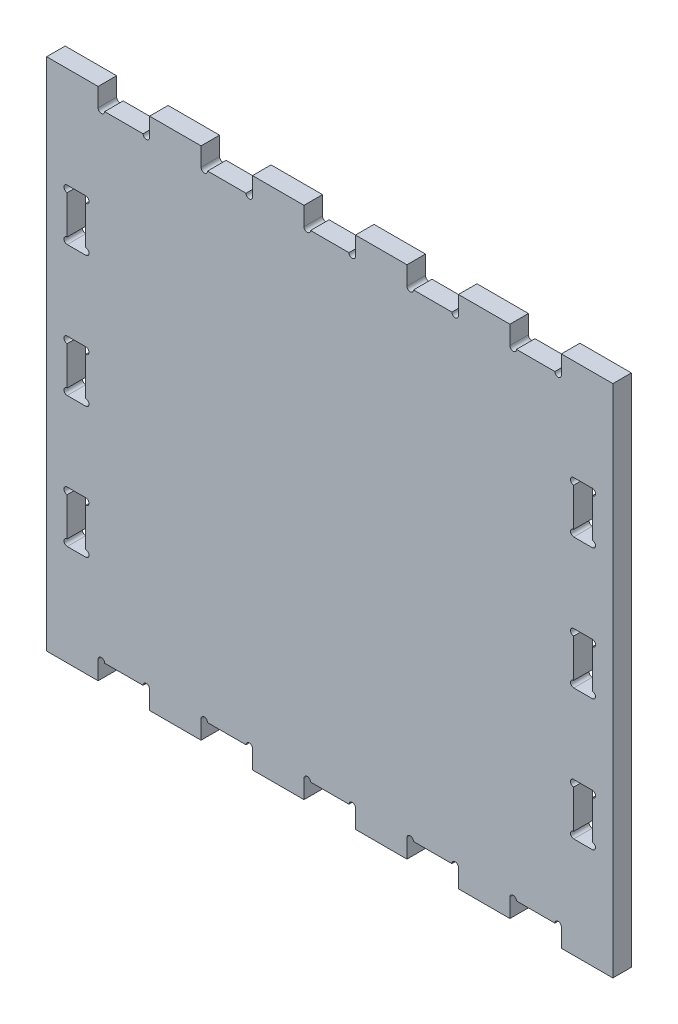
SolidWorks part; units mm, degrees
ref_plane "Piano frontale" through (0, 0, 0) normal (0, 0, 1) x (1, 0, 0)
ref_plane "Piano superiore" through (0, 0, 0) normal (0, 1, 0) x (1, 0, 0)
ref_plane "Piano destro" through (0, 0, 0) normal (1, 0, 0) x (0, 0, -1)
sketch "Schizzo2" plane through (0, 0, 0) normal (0, 0, 1) x (1, 0, 0)
  line L0 (-275, -250) -> (-275, 250)
  line L1 (-275, 250) -> (-225, 250)
  line L2 (-225, 250) -> (-225, 232)
  line L3 (-218.65, 232) -> (-181.35, 232)
  line L4 (-175, 232) -> (-175, 250)
  line L5 (-175, 250) -> (-125, 250)
  line L6 (-125, 250) -> (-125, 232)
  line L7 (-118.65, 232) -> (-81.35, 232)
  line L8 (-75, 232) -> (-75, 250)
  line L9 (-75, 250) -> (-25, 250)
  line L10 (-25, 250) -> (-25, 232)
  line L11 (-18.65, 232) -> (18.65, 232)
  line L12 (25, 232) -> (25, 250)
  line L13 (25, 250) -> (75, 250)
  line L14 (75, 250) -> (75, 232)
  line L15 (81.35, 232) -> (118.65, 232)
  line L16 (125, 232) -> (125, 250)
  line L17 (125, 250) -> (175, 250)
  line L18 (175, 250) -> (175, 232)
  line L19 (181.35, 232) -> (218.65, 232)
  line L20 (225, 232) -> (225, 250)
  line L21 (225, 250) -> (275, 250)
  line L22 (275, 250) -> (275, -250)
  line L23 (0, 0) -> (0, 370.058) construction
  line L24 (-255, 152) -> (-237, 152)
  line L25 (-255, 145.65) -> (-255, 108.35)
  line L26 (-255, 102) -> (-237, 102)
  line L27 (-237, 145.65) -> (-237, 108.35)
  line L28 (-275, 0) -> (275, 0) construction
  line L29 (237, 145.65) -> (237, 108.35)
  line L30 (255, 102) -> (237, 102)
  line L31 (255, 145.65) -> (255, 108.35)
  line L32 (255, 152) -> (237, 152)
  line L33 (255, -152) -> (237, -152)
  line L34 (255, -145.65) -> (255, -108.35)
  line L35 (255, -102) -> (237, -102)
  line L36 (237, -145.65) -> (237, -108.35)
  line L37 (-237, -145.65) -> (-237, -108.35)
  line L38 (-255, -102) -> (-237, -102)
  line L39 (-255, -145.65) -> (-255, -108.35)
  line L40 (-255, -152) -> (-237, -152)
  line L41 (225, -250) -> (275, -250)
  line L42 (225, -232) -> (225, -250)
  line L43 (181.35, -232) -> (218.65, -232)
  line L44 (175, -250) -> (175, -232)
  line L45 (125, -250) -> (175, -250)
  line L46 (125, -232) -> (125, -250)
  line L47 (81.35, -232) -> (118.65, -232)
  line L48 (75, -250) -> (75, -232)
  line L49 (25, -250) -> (75, -250)
  line L50 (25, -232) -> (25, -250)
  line L51 (-18.65, -232) -> (18.65, -232)
  line L52 (-25, -250) -> (-25, -232)
  line L53 (-75, -250) -> (-25, -250)
  line L54 (-75, -232) -> (-75, -250)
  line L55 (-118.65, -232) -> (-81.35, -232)
  line L56 (-125, -250) -> (-125, -232)
  line L57 (-175, -250) -> (-125, -250)
  line L58 (-175, -232) -> (-175, -250)
  line L59 (-218.65, -232) -> (-181.35, -232)
  line L60 (-225, -250) -> (-225, -232)
  line L61 (-275, -250) -> (-225, -250)
  line L62 (-255, 25) -> (-237, 25)
  line L63 (-237, -18.65) -> (-237, 18.65)
  line L64 (-255, -25) -> (-237, -25)
  line L65 (-255, -18.65) -> (-255, 18.65)
  line L66 (255, -18.65) -> (255, 18.65)
  line L67 (255, -25) -> (237, -25)
  line L68 (237, -18.65) -> (237, 18.65)
  line L69 (255, 25) -> (237, 25)
  arc A0 (-255, 145.65) -> (-255, 152) centre (-255, 148.825) cw
  arc A1 (-255, 108.35) -> (-255, 102) centre (-255, 105.175) ccw
  arc A2 (-237, 108.35) -> (-237, 102) centre (-237, 105.175) cw
  arc A3 (-237, 145.65) -> (-237, 152) centre (-237, 148.825) ccw
  arc A4 (237, 145.65) -> (237, 152) centre (237, 148.825) cw
  arc A5 (237, 108.35) -> (237, 102) centre (237, 105.175) ccw
  arc A6 (255, 108.35) -> (255, 102) centre (255, 105.175) cw
  arc A7 (255, 145.65) -> (255, 152) centre (255, 148.825) ccw
  arc A8 (255, -145.65) -> (255, -152) centre (255, -148.825) cw
  arc A9 (255, -108.35) -> (255, -102) centre (255, -105.175) ccw
  arc A10 (237, -108.35) -> (237, -102) centre (237, -105.175) cw
  arc A11 (237, -145.65) -> (237, -152) centre (237, -148.825) ccw
  arc A12 (-237, -145.65) -> (-237, -152) centre (-237, -148.825) cw
  arc A13 (-237, -108.35) -> (-237, -102) centre (-237, -105.175) ccw
  arc A14 (-255, -108.35) -> (-255, -102) centre (-255, -105.175) cw
  arc A15 (-255, -145.65) -> (-255, -152) centre (-255, -148.825) ccw
  arc A16 (-255, 18.65) -> (-255, 25) centre (-255, 21.825) cw
  arc A17 (-237, 18.65) -> (-237, 25) centre (-237, 21.825) ccw
  arc A18 (-255, -18.65) -> (-255, -25) centre (-255, -21.825) ccw
  arc A19 (-237, -18.65) -> (-237, -25) centre (-237, -21.825) cw
  arc A20 (237, -18.65) -> (237, -25) centre (237, -21.825) ccw
  arc A21 (255, -18.65) -> (255, -25) centre (255, -21.825) cw
  arc A22 (237, 18.65) -> (237, 25) centre (237, 21.825) cw
  arc A23 (255, 18.65) -> (255, 25) centre (255, 21.825) ccw
  arc A24 (225, 232) -> (218.65, 232) centre (221.825, 232) cw
  arc A25 (175, 232) -> (181.35, 232) centre (178.175, 232) ccw
  arc A26 (125, 232) -> (118.65, 232) centre (121.825, 232) cw
  arc A27 (75, 232) -> (81.35, 232) centre (78.175, 232) ccw
  arc A28 (25, 232) -> (18.65, 232) centre (21.825, 232) cw
  arc A29 (-25, 232) -> (-18.65, 232) centre (-21.825, 232) ccw
  arc A30 (-75, 232) -> (-81.35, 232) centre (-78.175, 232) cw
  arc A31 (-125, 232) -> (-118.65, 232) centre (-121.825, 232) ccw
  arc A32 (-175, 232) -> (-181.35, 232) centre (-178.175, 232) cw
  arc A33 (-225, 232) -> (-218.65, 232) centre (-221.825, 232) ccw
  arc A34 (-175, -232) -> (-181.35, -232) centre (-178.175, -232) ccw
  arc A35 (-225, -232) -> (-218.65, -232) centre (-221.825, -232) cw
  arc A36 (-75, -232) -> (-81.35, -232) centre (-78.175, -232) ccw
  arc A37 (-25, -232) -> (-18.65, -232) centre (-21.825, -232) cw
  arc A38 (25, -232) -> (18.65, -232) centre (21.825, -232) ccw
  arc A39 (75, -232) -> (81.35, -232) centre (78.175, -232) cw
  arc A40 (125, -232) -> (118.65, -232) centre (121.825, -232) ccw
  arc A41 (175, -232) -> (181.35, -232) centre (178.175, -232) cw
  arc A42 (225, -232) -> (218.65, -232) centre (221.825, -232) ccw
  arc A43 (-125, -232) -> (-118.65, -232) centre (-121.825, -232) cw
  point P31 (-258.175, 148.825)
  point P101 (-246, 25)
  point P127 (221.825, 228.825)
  point P129 (-121.825, -232)
  dimension "D20" = 3.175
  dimension "D2" = 50
  dimension "D3" = 50
  dimension "D4" = 18
  dimension "D5" = 18
  dimension "D8" = 2
  dimension "D9" = 3.175
  dimension "D10" = 50
  dimension "D11" = 18
  dimension "D12" = 20
  dimension "D13" = 80
  dimension "D14" = 250
  dimension "D15" = 0
  dimension "D16" = 275
  dimension "D18" = 25
  dimension "D19" = 3.175
  dimension "D6" = 4
  dimension "D7" = 2
  dimension "D17" = 2
  dimension "D21" = 5
  dimension "D22" = 2
extrude "Estrusione-Estrusione1" add sketch "Schizzo2" along normal blind 18 contours L0 L1 L2 A33 L3 A32 L4 L5 L6 A31 L7 A30 L8 L9 L10 A29 L11 A28 L12 L13 L14 A27 L15 A26 L16 L17 L18 A25 L19 A24 L20 L21 L22 L41 L42 A42 L43 A41 L44 L45 L46 A40 L47 A39 L48 L49 L50 A38 L51 A37 L52 L53 L54 A36 L55 A43 L56 L57 L58 A34 L59 A35 L60 L61
extrude "Taglio-Estrusione1" cut sketch "Schizzo2<4>" along normal blind 115 contours L29 A5 L30 A6 L31 A7 L32 A4
sketch "Schizzo2<4>" plane through (0, 0, 0) normal (0, 0, 1) x (1, 0, 0) same geometry as "Schizzo2"
extrude "Taglio-Estrusione2" cut sketch "Schizzo2<5>" along normal blind 258 contours L68 A22 L69 A23 L66 A21 L67 A20
sketch "Schizzo2<5>" plane through (0, 0, 0) normal (0, 0, 1) x (1, 0, 0) same geometry as "Schizzo2"
extrude "Taglio-Estrusione3" cut sketch "Schizzo2<7>" along normal blind 723 contours L36 A10 L35 A9 L34 A8 L33 A11
sketch "Schizzo2<7>" plane through (0, 0, 0) normal (0, 0, 1) x (1, 0, 0) same geometry as "Schizzo2"
extrude "Taglio-Estrusione4" cut sketch "Schizzo2<8>" along normal blind 160 contours L25 A1 L26 A2 L27 A3 L24 A0
sketch "Schizzo2<8>" plane through (0, 0, 0) normal (0, 0, 1) x (1, 0, 0) same geometry as "Schizzo2"
extrude "Taglio-Estrusione5" cut sketch "Schizzo2<9>" along normal blind 190 contours L65 A16 L62 A17 L63 A19 L64 A18
sketch "Schizzo2<9>" plane through (0, 0, 0) normal (0, 0, 1) x (1, 0, 0) same geometry as "Schizzo2"
extrude "Taglio-Estrusione6" cut sketch "Schizzo2<10>" along normal blind 231 contours L39 A14 L38 A13 L37 A12 L40 A15
sketch "Schizzo2<10>" plane through (0, 0, 0) normal (0, 0, 1) x (1, 0, 0) same geometry as "Schizzo2"
